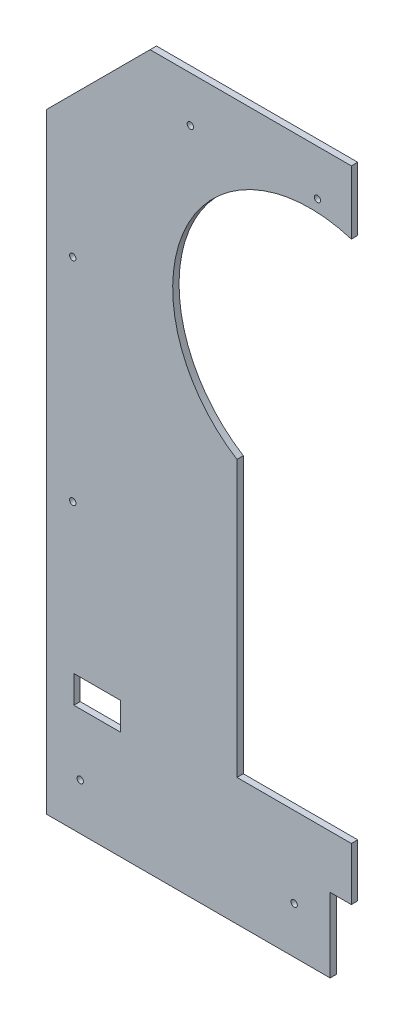
SolidWorks part; units mm, degrees
ref_plane "Front" through (0, 0, 0) normal (0, 0, 1) x (1, 0, 0)
ref_plane "Top" through (0, 0, 0) normal (0, 1, 0) x (1, 0, 0)
ref_plane "Right" through (0, 0, 0) normal (1, 0, 0) x (0, 0, -1)
sketch "Esquisse1" plane through (0, 0, 0) normal (0, 0, 1) x (1, 0, 0)
  line L1 (0, 0) -> (144, 0)
  line L2 (0, 0) -> (0, 337)
  line L3 (0, 337) -> (144, 337)
  line L4 (144, 0) -> (144, 337)
  dimension "D1" = 144
  dimension "D2" = 337
extrude "Boss.-Extru.1" add sketch "Esquisse1" along normal blind 3
sketch "Esquisse2" plane through (0, 0, 3) normal (0, 0, 1) x (1, 0, 0)
  line L0 (0, 22) -> (16, 22) construction
  line L1 (0, 337) -> (0, 0) construction
  line L2 (0, 0) -> (144, 0) construction
  line L3 (12.5, 134) -> (12.5, 234) construction
  line L4 (68, 315.5) -> (128, 315.5) construction
  line L5 (72, 0) -> (72, 12.3457) construction
  line L6 (16, 22) -> (117, 22) construction
  circle A0 centre (16, 22) radius 1.5
  circle A1 centre (12.5, 234) radius 1.5
  circle A2 centre (12.5, 134) radius 1.5
  circle A3 centre (68, 315.5) radius 1.5
  circle A4 centre (128, 315.5) radius 1.5
  circle A5 centre (117, 22) radius 1.5
  point P19 (0, 0)
  dimension "D1" = 3
  dimension "D7" = 55.5
  dimension "D10" = 45
  dimension "D2" = 16
  dimension "D3" = 22
  dimension "D4" = 112
  dimension "D5" = 3.5
  dimension "D6" = 100
  dimension "D8" = 81.5
  dimension "D9" = 60
extrude "Enlèv. mat.-Extru.1" cut sketch "Esquisse2" against normal through all
chamfer "Chanfrein1" distance 49 angle 45 1 edges at (0, 337, 1.5)
sketch "Esquisse3" plane through (0, 0, 3) normal (0, 0, 1) x (1, 0, 0)
  line L0 (144, 0) -> (144, 337) construction
  line L1 (0, 0) -> (144, 0) construction
  line L2 (134, 0) -> (144, 0)
  line L3 (134, 0) -> (134, 35)
  line L4 (134, 35) -> (144, 35)
  line L5 (144, 0) -> (144, 35)
  dimension "D1" = 10
  dimension "D2" = 35
extrude "Enlèv. mat.-Extru.2" cut sketch "Esquisse3" against normal through all and the other way through all
sketch "Esquisse4" plane through (0, 0, 3) normal (0, 0, 1) x (1, 0, 0)
  line L0 (0, 288) -> (0, 0) construction
  line L1 (13, 64) -> (35, 64)
  line L2 (13, 64) -> (13, 51)
  line L3 (13, 51) -> (35, 51)
  line L4 (35, 64) -> (35, 51)
  line L5 (0, 0) -> (134, 0) construction
  dimension "D1" = 13
  dimension "D2" = 22
  dimension "D3" = 13
  dimension "D4" = 51
extrude "Enlèv. mat.-Extru.3" cut sketch "Esquisse4" against normal through all
sketch "Esquisse5" plane through (0, 0, 3) normal (0, 0, 1) x (1, 0, 0)
  line L0 (144, 60) -> (90, 60)
  line L1 (144, 35) -> (144, 337) construction
  line L2 (90, 60) -> (90, 190)
  line L3 (144, 60) -> (144, 307.0435)
  line L4 (0, 0) -> (134, 0) construction
  arc A0 (90, 190) -> (144, 307.0435) centre (124.6622, 244.9867) cw
  point P9 (124.4747, 244.107)
  point P10 (129.465, 240.1942)
  point P11 (124.6622, 244.9867)
  dimension "D4" = 65
  dimension "D1" = 54
  dimension "D2" = 60
  dimension "D3" = 130
extrude "Enlèv. mat.-Extru.4" cut sketch "Esquisse5" against normal through all
